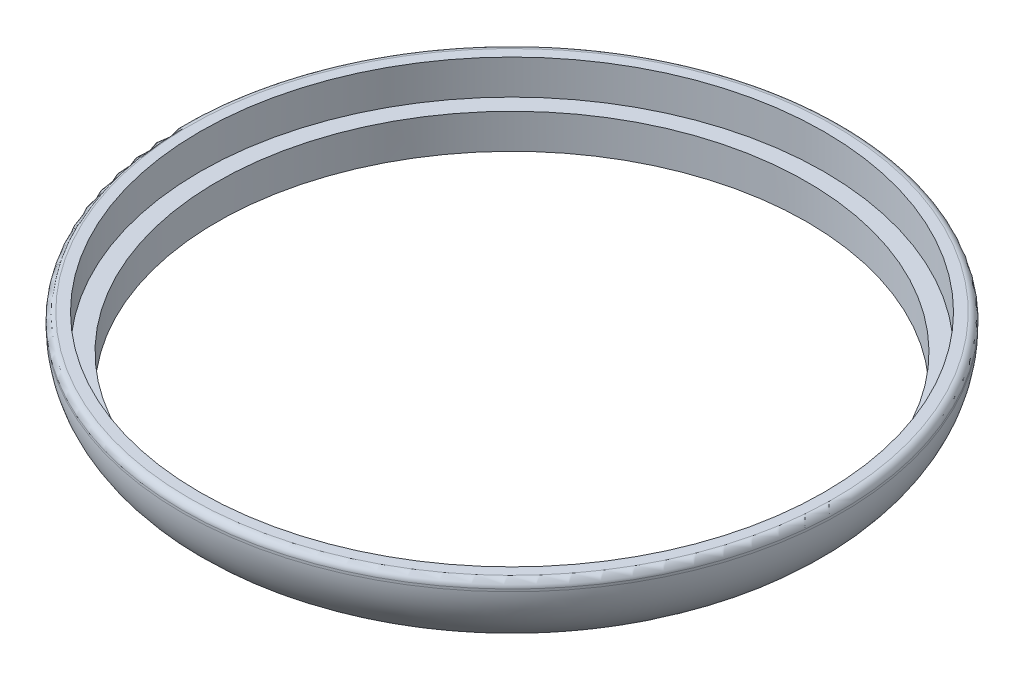
SolidWorks part; units mm, degrees
ref_plane "Front Plane" through (0, 0, 0) normal (0, 0, 1) x (1, 0, 0)
ref_plane "Top Plane" through (0, 0, 0) normal (0, 1, 0) x (1, 0, 0)
ref_plane "Right Plane" through (0, 0, 0) normal (1, 0, 0) x (0, 0, -1)
sketch "Sketch1" plane through (0, 0, 0) normal (0, 1, 0) x (1, 0, 0)
  circle A0 centre (0, 0) radius 4.75
  circle A1 centre (0, 0) radius 4.25
  dimension "D1" = 9.5
  dimension "D2" = 8.5
extrude "Boss-Extrude1" add sketch "Sketch1" along normal blind 1
sketch "Sketch2" plane through (0, 1, 0) normal (0, 1, 0) x (1, 0, 0)
  circle A2 centre (0, 0) radius 4.5
  circle A3 centre (0, 0) radius 4.5
  dimension "D1" = 0.25
extrude "Cut-Extrude1" cut sketch "Sketch2" against normal blind 0.5
fillet "Fillet1" radius 1 1 edges at (0, 0, 4.75)
fillet "Fillet2" radius 0.1 1 edges at (0, 1, 4.75)
